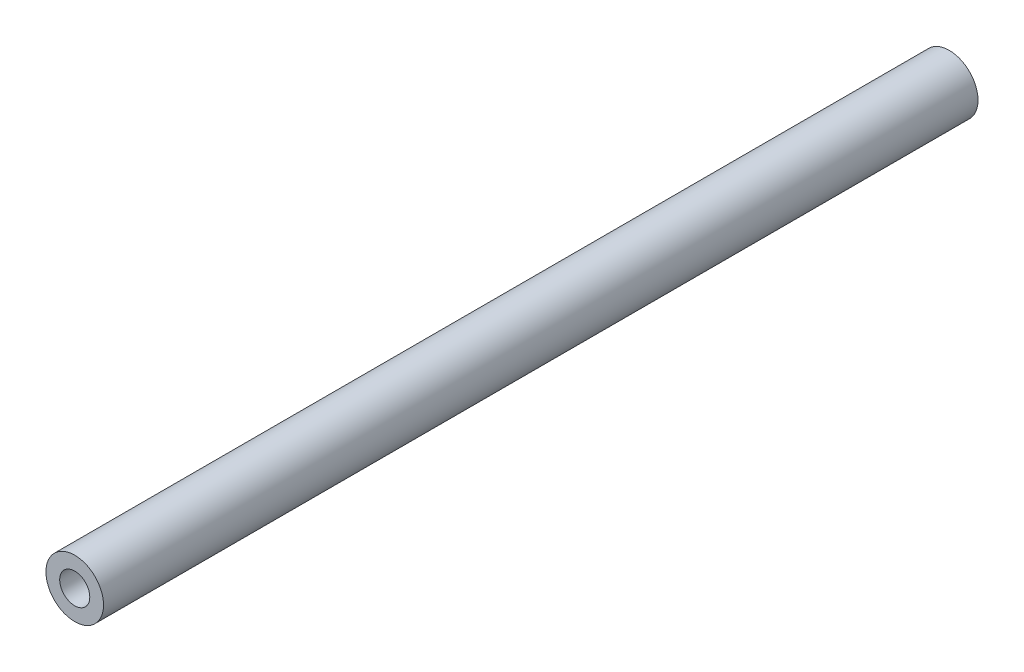
SolidWorks part; units mm, degrees
material "6061-T6 (SS)"
ref_plane "Front Plane" through (0, 0, 0) normal (0, 0, 1) x (1, 0, 0)
ref_plane "Top Plane" through (0, 0, 0) normal (0, 1, 0) x (1, 0, 0)
ref_plane "Right Plane" through (0, 0, 0) normal (1, 0, 0) x (0, 0, -1)
sketch "Sketch1" plane through (0, 0, 0) normal (0, 0, 1) x (1, 0, 0)
  circle A0 centre (0, 0) radius 4.7625
  circle A1 centre (0, 0) radius 2.4892
  dimension "D1" = 9.525
  dimension "D2" = 4.9784
extrude "Boss-Extrude1" add sketch "Sketch1" against normal blind 144.6784
